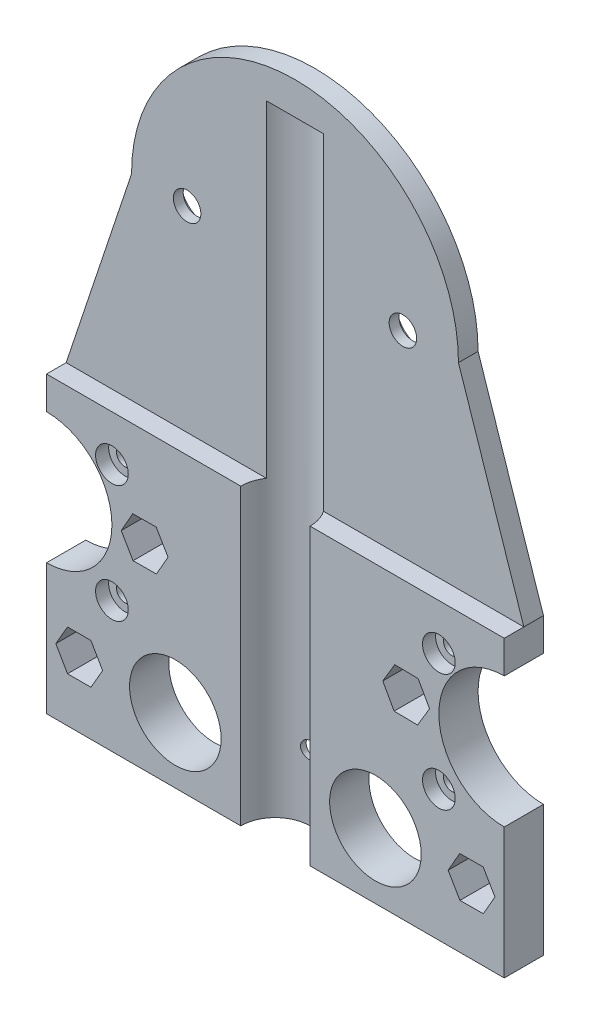
SolidWorks part; units mm, degrees
ref_plane "前视基准面" through (0, 0, 0) normal (0, 0, 1) x (1, 0, 0)
ref_plane "上视基准面" through (0, 0, 0) normal (0, 1, 0) x (1, 0, 0)
ref_plane "右视基准面" through (0, 0, 0) normal (1, 0, 0) x (0, 0, -1)
sketch "草图1" plane through (0, 0, 0) normal (0, 0, 1) x (1, 0, 0)
  line L0 (0, 0) -> (35, 0)
  line L1 (-35, 0) -> (-35, 100)
  line L2 (0, 0) -> (-35, 0)
  line L3 (-35, 100) -> (35, 100)
  line L4 (35, 100) -> (35, 0)
  line L6 (0, 100) -> (0, 75) construction
  line L7 (0, 75) -> (16.5, 75) construction
  line L8 (0, 75) -> (-16.5, 75) construction
  line L9 (0, 75) -> (0, 45) construction
  line L10 (0, 45) -> (35, 45)
  line L11 (0, 45) -> (-35, 45)
  line L12 (0, 30) -> (20, 30) construction
  line L13 (0, 10) -> (30, 10) construction
  line L14 (0, 10) -> (-30, 10) construction
  line L15 (0, 10) -> (0, 20) construction
  line L16 (0, 20) -> (25, 20) construction
  line L17 (0, 20) -> (-25, 20) construction
  line L18 (0, 20) -> (0, 30) construction
  line L19 (0, 30) -> (-20, 30) construction
  line L20 (0, 30) -> (0, 38) construction
  line L21 (-18.1877, 26.9131) -> (-16.4205, 30.0261)
  line L22 (-16.4205, 30.0261) -> (-18.2329, 33.113)
  line L23 (-18.2329, 33.113) -> (-21.8123, 33.0869)
  line L24 (-21.8123, 33.0869) -> (-23.5795, 29.9739)
  line L25 (-23.5795, 29.9739) -> (-21.7671, 26.887)
  line L26 (-21.7671, 26.887) -> (-18.1877, 26.9131)
  line L27 (-28.2084, 6.9011) -> (-26.4204, 10.0021)
  line L28 (-26.4204, 10.0021) -> (-28.2121, 13.1011)
  line L29 (-28.2121, 13.1011) -> (-31.7916, 13.0989)
  line L30 (-31.7916, 13.0989) -> (-33.5796, 9.9979)
  line L31 (-33.5796, 9.9979) -> (-31.7879, 6.8989)
  line L32 (-31.7879, 6.8989) -> (-28.2084, 6.9011)
  line L33 (21.7412, 26.8724) -> (23.5791, 29.9441)
  line L34 (23.5791, 29.9441) -> (21.8379, 33.0717)
  line L35 (21.8379, 33.0717) -> (18.2588, 33.1276)
  line L36 (18.2588, 33.1276) -> (16.4209, 30.0559)
  line L37 (16.4209, 30.0559) -> (18.1621, 26.9283)
  line L38 (18.1621, 26.9283) -> (21.7412, 26.8724)
  line L39 (31.8047, 6.9087) -> (33.5795, 10.0172)
  line L40 (33.5795, 10.0172) -> (31.7748, 13.1086)
  line L41 (31.7748, 13.1086) -> (28.1953, 13.0913)
  line L42 (28.1953, 13.0913) -> (26.4205, 9.9828)
  line L43 (26.4205, 9.9828) -> (28.2252, 6.8914)
  line L44 (28.2252, 6.8914) -> (31.8047, 6.9087)
  line L45 (0, 38) -> (-25, 38) construction
  line L46 (0, 38) -> (25, 38) construction
  circle A0 centre (-16.5, 75) radius 2.1
  circle A1 centre (16.5, 75) radius 2.1
  circle A2 centre (0, 10) radius 1.3
  circle A3 centre (-25, 20) radius 1.3
  circle A4 centre (25, 20) radius 1.3
  circle A5 centre (-20, 30) radius 3.1 construction
  circle A6 centre (-30, 10) radius 3.1 construction
  circle A7 centre (20, 30) radius 3.1 construction
  circle A8 centre (30, 10) radius 3.1 construction
  circle A9 centre (25, 38) radius 1.3
  circle A10 centre (-25, 38) radius 1.3
extrude "凸台-拉伸1" add sketch "草图1" along normal blind 6 contours L10 L11 L2 L0 A4 A3 A2 L44 L43 L42 L41 L40 L39 L38 L37 L36 L35 L34 L33 L32 L31 L30 L29 L28 L27 L26 L25 L24 L23 L22 L21 region at (0, 22.5874, 0)
extrude "凸台-拉伸2" add sketch "草图1<3>" along normal blind 3 contours L11 L10 A1 A0 region at (0, 72.4819, 0)
sketch "草图1<3>" plane through (0, 0, 0) normal (0, 0, 1) x (1, 0, 0) same geometry as "草图1"
sketch "草图3" plane through (0, 0, 0) normal (0, -1, 0) x (-1, 0, 0)
  line L0 (0, 0) -> (0, -6) construction
  line L1 (-35, -6) -> (35, -6) construction
  circle A0 centre (0, -6) radius 5.3
extrude "切除-拉伸1" cut sketch "草图3" against normal blind 95
sketch "草图6" plane through (0, 0, 0) normal (0, 0, -1) x (-1, 0, 0)
  circle A0 centre (25, 38) radius 3.2
  circle A1 centre (25, 20) radius 3.2
  circle A2 centre (-25, 20) radius 3.2
  circle A3 centre (-25, 38) radius 3
extrude "切除-拉伸3" cut sketch "草图6" against normal blind 2
sketch "草图9" plane through (0, 0, 0) normal (0, 0, -1) x (-1, 0, 0)
  circle A0 centre (-16.5, 75) radius 4
  circle A1 centre (16.5, 75) radius 4
extrude "切除-拉伸6" cut sketch "草图9" against normal blind 1.5
sketch "草图10" plane through (0, 0, 3) normal (0, 0, 1) x (1, 0, 0)
  line L0 (-16.5, 75) -> (16.5, 75) construction
  line L2 (-35, 100) -> (35, 100) construction
  line L4 (-25, 75) -> (-35, 45)
  line L5 (-35, 45) -> (-35, 100)
  line L6 (-35, 45) -> (-35, 100) construction
  line L7 (-35, 100) -> (0, 100)
  line L8 (0, 100) -> (-0.3237, 100.2602)
  line L9 (25, 75) -> (35, 45)
  line L10 (35, 45) -> (35, 100)
  line L11 (35, 100) -> (-0.3237, 100.2602)
  arc A0 (0, 100) -> (-25, 75) centre (0, 75) ccw
  arc A1 (0, 100) -> (25, 75) centre (0, 75) cw
  line M6 (35, 45) -> (35, 100)
  line M7 (35, 100) -> (-35, 100)
  line M8 (-35, 100) -> (-35, 45)
extrude "切除-拉伸7" cut sketch "草图10" against normal through all contours A0 L4 M7 M8 | A1 L9 M7 M6 region at (27.8102, 82.9179, 3) region at (-27.8102, 82.9179, 3)
sketch "草图11" plane through (0, 0, 6) normal (0, 0, 1) x (1, 0, 0)
  line L0 (-35, 45) -> (-35, 30)
  line L1 (-35, 0) -> (-35, 45) construction
  line L2 (-35, 30) -> (-35, 20)
  line L3 (35, 45) -> (35, 30)
  line L4 (35, 45) -> (35, 0) construction
  line L5 (35, 30) -> (35, 20)
  circle A0 centre (-35, 30) radius 10
  circle A1 centre (35, 30) radius 10
  line M3 (-35, 45) -> (-35, 0)
extrude "切除-拉伸8" cut sketch "草图11" against normal through all contours L3 A1 L5 | A0 L0 M3 region at (-30.7559, 30, 6) region at (30.7559, 30, 6)
sketch "草图12" plane through (0, 0, 6) normal (0, 0, 1) x (1, 0, 0)
  line L0 (-5.3, 0) -> (-15.3, 0)
  line L1 (-5.3, 0) -> (-35, 0) construction
  line L2 (-15.3, 0) -> (-15.3, 10) construction
  line L3 (5.3, 0) -> (15.3, 0)
  line L4 (35, 0) -> (5.3, 0) construction
  line L5 (15.3, 0) -> (15.3, 10) construction
  circle A0 centre (-15.3, 10) radius 7
  circle A1 centre (15.3, 10) radius 7
extrude "切除-拉伸9" cut sketch "草图12" against normal through all contours A1 | A0 region at (-15.3, 10, 6) region at (15.3, 10, 6)
sketch "草图13" plane through (0, 0, 6) normal (0, 0, 1) x (1, 0, 0)
  circle A0 centre (-25, 20) radius 2.5
  circle A1 centre (25, 20) radius 2.5
  circle A2 centre (25, 38) radius 2.5
  circle A3 centre (-25, 38) radius 2.5
extrude "切除-拉伸11" cut sketch "草图13" against normal blind 2
